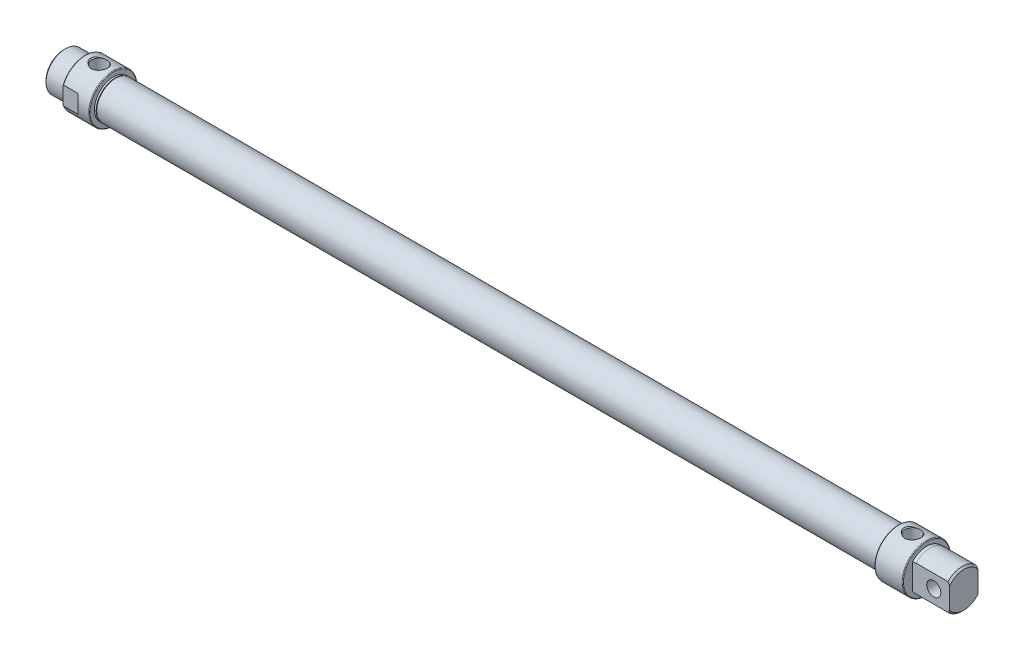
SolidWorks part; units mm, degrees
ref_plane "前视基准面" through (0, 0, 0) normal (0, 0, 1) x (1, 0, 0)
ref_plane "上视基准面" through (0, 0, 0) normal (0, 1, 0) x (1, 0, 0)
ref_plane "右视基准面" through (0, 0, 0) normal (1, 0, 0) x (0, 0, -1)
sketch "草图1" plane through (0, 0, 0) normal (0, 0, 1) x (1, 0, 0)
  line L0 (0, 0) -> (0, 10.08)
  line L1 (0, 10.08) -> (0.92, 11)
  line L2 (0.92, 11) -> (12, 11)
  line L3 (12, 11) -> (12, 13.1)
  line L4 (12.4, 13.5) -> (27.6, 13.5)
  line L5 (28, 13.1) -> (28, 10.7)
  line L6 (28, 10.7) -> (29, 10.7)
  line L7 (29, 10.7) -> (29, 10.2)
  line L8 (29, 10.2) -> (29.3, 10.7)
  line L9 (29.3, 10.7) -> (470.7, 10.7)
  line L10 (470.7, 10.7) -> (471, 10.2)
  line L11 (471, 10.2) -> (471, 10.7)
  line L12 (471, 10.7) -> (472, 10.7)
  line L13 (472, 10.7) -> (472, 13.1)
  line L14 (472.4, 13.5) -> (487.6, 13.5)
  line L15 (488, 13.1) -> (488, 0)
  line L16 (488, 0) -> (0, 0)
  line L17 (488, 0) -> (0, 0) construction
  arc A0 (12, 13.1) -> (12.4, 13.5) centre (12.4, 13.1) cw
  arc A1 (27.6, 13.5) -> (28, 13.1) centre (27.6, 13.1) cw
  arc A2 (472, 13.1) -> (472.4, 13.5) centre (472.4, 13.1) cw
  arc A3 (487.6, 13.5) -> (488, 13.1) centre (487.6, 13.1) cw
revolve "旋转1" add sketch "草图1" angle 360 about L17 reverse direction yes
cosmetic thread "装饰螺纹线1" parameters "D1"=10, "D2"=20.16
sketch "草图2" plane through (0, 0, 0) normal (0, 0, 1) x (1, 0, 0)
  line L0 (488, 0) -> (488, 10.85)
  line L1 (488, 10.85) -> (490, 10.85)
  line L2 (490, 10.85) -> (490, 11)
  line L3 (490, 11) -> (508, 11)
  line L4 (508, 11) -> (509, 10)
  line L5 (509, 10) -> (509, 0)
  line L6 (509, 0) -> (488, 0)
  line L7 (509, 0) -> (488, 0) construction
revolve "旋转2" add sketch "草图2" angle 360 about L7 reverse direction yes
cosmetic thread "装饰螺纹线2" parameters "D1"=19, "D2"=18.933
ref_plane "基准面4" through (12, 0, 0) normal (1, 0, 0) x (0, 0, -1)
ref_plane "基准面5" through (509, 0, 0) normal (1, 0, 0) x (0, 0, -1)
sketch "草图3" plane through (509, 0, 0) normal (1, 0, 0) x (0, 0, -1)
  line L0 (-18, 21) -> (-18, -21)
  line L1 (-18, -21) -> (18, -21)
  line L2 (18, -21) -> (18, 21)
  line L3 (18, 21) -> (-18, 21)
  line L4 (-8, 11) -> (-8, -11)
  line L5 (-8, -11) -> (8, -11)
  line L6 (8, -11) -> (8, 11)
  line L7 (8, 11) -> (-8, 11)
extrude "切除-拉伸1" cut sketch "草图3" against normal blind 21
ref_plane "基准面6" through (500, 0, 0) normal (1, 0, 0) x (0, 0, -1)
sketch "草图4" plane through (500, 0, 0) normal (1, 0, 0) x (0, 0, -1)
  line L0 (-8, 0) -> (-8, 4)
  line L1 (-8, 4) -> (8, 4)
  line L2 (8, 4) -> (8, 0)
  line L3 (8, 0) -> (-8, 0)
  line L4 (8, 0) -> (-8, 0) construction
revolve "切除-旋转1" cut sketch "草图4" angle 360 about L4 reverse direction yes
sketch "草图5" plane through (0, 0, 0) normal (0, 0, 1) x (1, 0, 0)
  line L0 (20, 13.5) -> (24.864, 13.5)
  line L1 (24.864, 13.5) -> (24.283, 12.919)
  line L2 (24.283, 12.919) -> (24.283, 5.5)
  line L3 (24.283, 5.5) -> (20, 5.5)
  line L4 (20, 5.5) -> (20, 13.5)
  line L5 (20, 5.5) -> (20, 13.5) construction
revolve "切除-旋转2" cut sketch "草图5" angle 360 about L5 reverse direction yes
cosmetic thread "装饰螺纹线3" parameters "D1"=7.419, "D2"=9.728
sketch "草图6" plane through (0, 0, 0) normal (0, 0, 1) x (1, 0, 0)
  line L0 (480, 13.5) -> (484.864, 13.5)
  line L1 (484.864, 13.5) -> (484.283, 12.919)
  line L2 (484.283, 12.919) -> (484.283, 5.5)
  line L3 (484.283, 5.5) -> (480, 5.5)
  line L4 (480, 5.5) -> (480, 13.5)
  line L5 (480, 5.5) -> (480, 13.5) construction
revolve "切除-旋转3" cut sketch "草图6" angle 360 about L5 reverse direction yes
cosmetic thread "装饰螺纹线4" parameters "D1"=7.419, "D2"=9.728
sketch "草图7" plane through (0, 0, 0) normal (0, 1, 0) x (1, 0, 0)
  line L0 (-4, -13.5) -> (21.5, -13.5)
  line L1 (21.5, -13.5) -> (20.5, -12.5)
  line L2 (20.5, -12.5) -> (-2, -12.5)
  line L3 (-2, -12.5) -> (-2, 12.5)
  line L4 (-2, 12.5) -> (20.5, 12.5)
  line L5 (20.5, 12.5) -> (21.5, 13.5)
  line L6 (21.5, 13.5) -> (-4, 13.5)
  line L7 (-4, 13.5) -> (-4, -13.5)
extrude "切除-拉伸2" cut sketch "草图7" along normal blind 27 and the other way blind 27
sketch "草图8" plane through (0, 0, 0) normal (0, 0, 1) x (1, 0, 0)
  line L0 (0, 0) -> (0, 4)
  line L1 (0, 4) -> (39, 4)
  line L2 (39, 4) -> (39, 10)
  line L3 (39, 10) -> (461, 10)
  line L4 (461, 10) -> (461, 0)
  line L5 (461, 0) -> (0, 0)
  line L6 (461, 0) -> (0, 0) construction
revolve "切除-旋转4" cut sketch "草图8" angle 360 about L6 reverse direction yes
ref_plane "基准面7" through (20, 0, 0) normal (1, 0, 0) x (0, 0, -1)
ref_plane "基准面8" through (0, 16.8, 0) normal (0, 1, 0) x (1, 0, 0)
ref_plane "基准面9" through (480, 0, 0) normal (1, 0, 0) x (0, 0, -1)
ref_plane "基准面10" through (4.5, 0, 0) normal (1, 0, 0) x (0, 0, -1)
ref_plane "基准面11" through (28, 0, 0) normal (1, 0, 0) x (0, 0, -1)
ref_plane "基准面12" through (12, 0, 0) normal (1, 0, 0) x (0, 0, -1)
ref_plane "基准面13" through (488, 0, 0) normal (1, 0, 0) x (0, 0, -1)
ref_plane "基准面14" through (495.5, 0, 0) normal (1, 0, 0) x (0, 0, -1)
ref_plane "基准面15" through (29, 0, 0) normal (1, 0, 0) x (0, 0, -1)
ref_plane "基准面16" through (471, 0, 0) normal (1, 0, 0) x (0, 0, -1)
ref_plane "IP_SWITCH1 XY" through (29, 0, 0) normal (-1, 0, 0) x (0, 0, 1)
ref_plane "IP_SWITCH1 XZ" through (0, 0, 0) normal (0, 1, 0) x (1, 0, 0)
ref_plane "IP_SWITCH1 YZ" through (0, 0, 0) normal (0, 0, -1) x (-1, 0, 0)
ref_axis "IP_SWITCH1 X" through (29, 0, 80.9) along (0, 0, -1)
ref_axis "IP_SWITCH1 Y" through (29, 50, 0) along (0, -1, 0)
ref_axis "IP_SWITCH1 Z" through (-80.9, 0, 0) along (1, 0, 0)
sketch3d "IP_SWITCH1"
  point P0 (29, 0, 0)
ref_plane "IP_SWITCH2 XY" through (471, 0, 0) normal (1, 0, 0) x (0, 0, -1)
ref_plane "IP_SWITCH2 XZ" through (0, 0, 0) normal (0, -1, 0) x (-1, 0, 0)
ref_plane "IP_SWITCH2 YZ" through (0, 0, 0) normal (0, 0, -1) x (-1, 0, 0)
ref_axis "IP_SWITCH2 X" through (471, 0, 80.9) along (0, 0, -1)
ref_axis "IP_SWITCH2 Y" through (471, -50, 0) along (0, 1, 0)
ref_axis "IP_SWITCH2 Z" through (80.9, 0, 0) along (-1, 0, 0)
sketch3d "IP_SWITCH2"
  point P0 (471, 0, 0)
ref_plane "body-dummy XY" through (28, 0, 0) normal (1, 0, 0) x (0, 0, -1)
ref_plane "body-dummy XZ" through (0, 0, 0) normal (0, -1, 0) x (-1, 0, 0)
ref_plane "body-dummy YZ" through (0, 0, 0) normal (0, 0, -1) x (-1, 0, 0)
ref_axis "body-dummy X" through (28, 0, 80.9) along (0, 0, -1)
ref_axis "body-dummy Y" through (28, -50, 0) along (0, 1, 0)
ref_axis "body-dummy Z" through (80.9, 0, 0) along (-1, 0, 0)
sketch3d "body-dummy"
  point P0 (28, 0, 0)
ref_plane "body-sdb XY" through (0, 0, 0) normal (0, 0, 1) x (1, 0, 0)
ref_plane "body-sdb XZ" through (0, 0, 0) normal (0, -1, 0) x (-1, 0, 0)
ref_plane "body-sdb YZ" through (500, 0, 0) normal (1, 0, 0) x (0, 0, -1)
ref_axis "body-sdb X" through (-80.9, 0, 0) along (1, 0, 0)
ref_axis "body-sdb Y" through (500, -50, 0) along (0, 1, 0)
ref_axis "body-sdb Z" through (500, 0, 80.9) along (0, 0, -1)
sketch3d "body-sdb"
  point P0 (500, 0, 0)
ref_plane "fa-body XY" through (12, 0, 0) normal (-1, 0, 0) x (0, 0, 1)
ref_plane "fa-body XZ" through (0, 0, 0) normal (0, 1, 0) x (1, 0, 0)
ref_plane "fa-body YZ" through (0, 0, 0) normal (0, 0, -1) x (-1, 0, 0)
ref_axis "fa-body X" through (12, 0, 80.9) along (0, 0, -1)
ref_axis "fa-body Y" through (12, 50, 0) along (0, -1, 0)
ref_axis "fa-body Z" through (-80.9, 0, 0) along (1, 0, 0)
sketch3d "fa-body"
  point P0 (12, 0, 0)
ref_plane "lb-body XY" through (488, 0, 0) normal (1, 0, 0) x (0, 0, -1)
ref_plane "lb-body XZ" through (0, 0, 0) normal (0, -1, 0) x (-1, 0, 0)
ref_plane "lb-body YZ" through (0, 0, 0) normal (0, 0, -1) x (-1, 0, 0)
ref_axis "lb-body X" through (488, 0, 80.9) along (0, 0, -1)
ref_axis "lb-body Y" through (488, -50, 0) along (0, 1, 0)
ref_axis "lb-body Z" through (80.9, 0, 0) along (-1, 0, 0)
sketch3d "lb-body"
  point P0 (488, 0, 0)
ref_plane "nut1-body XY" through (495.5, 0, 0) normal (1, 0, 0) x (0, 0, -1)
ref_plane "nut1-body XZ" through (0, 0, 0) normal (0, -1, 0) x (-1, 0, 0)
ref_plane "nut1-body YZ" through (0, 0, 0) normal (0, 0, -1) x (-1, 0, 0)
ref_axis "nut1-body X" through (495.5, 0, 80.9) along (0, 0, -1)
ref_axis "nut1-body Y" through (495.5, -50, 0) along (0, 1, 0)
ref_axis "nut1-body Z" through (80.9, 0, 0) along (-1, 0, 0)
sketch3d "nut1-body"
  point P0 (495.5, 0, 0)
ref_plane "nut2-body XY" through (4.5, 0, 0) normal (-1, 0, 0) x (0, 0, 1)
ref_plane "nut2-body XZ" through (0, 0, 0) normal (0, 1, 0) x (1, 0, 0)
ref_plane "nut2-body YZ" through (0, 0, 0) normal (0, 0, -1) x (-1, 0, 0)
ref_axis "nut2-body X" through (4.5, 0, 80.9) along (0, 0, -1)
ref_axis "nut2-body Y" through (4.5, 50, 0) along (0, -1, 0)
ref_axis "nut2-body Z" through (-80.9, 0, 0) along (1, 0, 0)
sketch3d "nut2-body"
  point P0 (4.5, 0, 0)
ref_plane "rod-body XY" through (0, 0, 0) normal (-1, 0, 0) x (0, 0, 1)
ref_plane "rod-body XZ" through (0, 0, 0) normal (0, 1, 0) x (1, 0, 0)
ref_plane "rod-body YZ" through (0, 0, 0) normal (0, 0, -1) x (-1, 0, 0)
ref_axis "rod-body X" through (0, 0, 80.9) along (0, 0, -1)
ref_axis "rod-body Y" through (0, 50, 0) along (0, -1, 0)
ref_axis "rod-body Z" through (-80.9, 0, 0) along (1, 0, 0)
sketch3d "rod-body"
  point P0 (0, 0, 0)
ref_plane "rod-nut XY" through (0, 0, 0) normal (-1, 0, 0) x (0, 0, 1)
ref_plane "rod-nut XZ" through (0, 0, 0) normal (0, 1, 0) x (1, 0, 0)
ref_plane "rod-nut YZ" through (0, 0, 0) normal (0, 0, -1) x (-1, 0, 0)
ref_axis "rod-nut X" through (0, 0, 80.9) along (0, 0, -1)
ref_axis "rod-nut Y" through (0, 50, 0) along (0, -1, 0)
ref_axis "rod-nut Z" through (-80.9, 0, 0) along (1, 0, 0)
sketch3d "rod-nut"
  point P0 (0, 0, 0)
